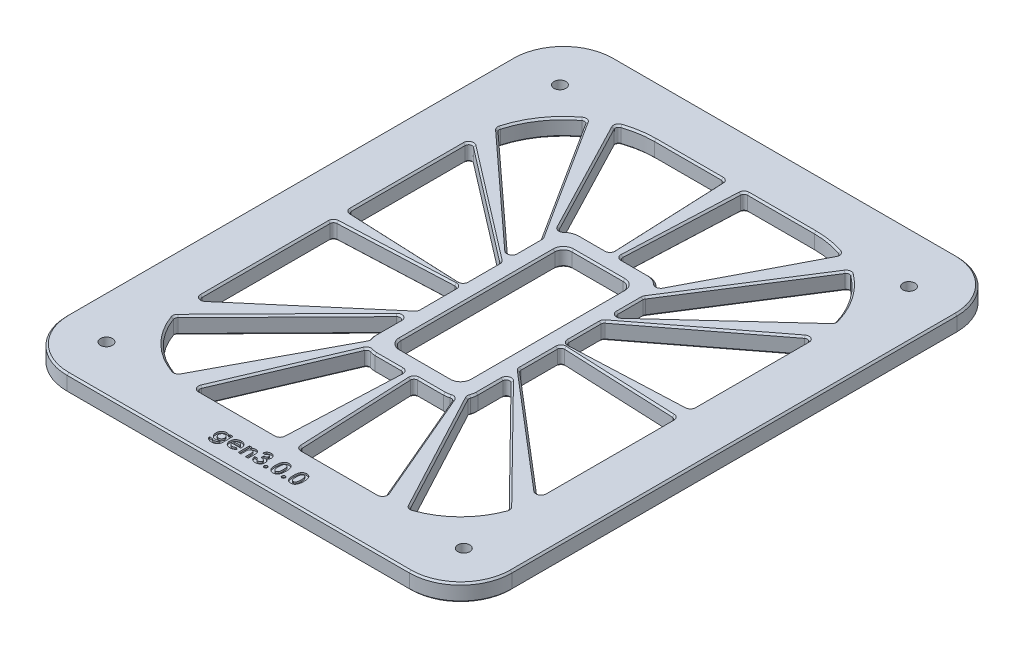
SolidWorks part; units mm, degrees
ref_plane "Front Plane" through (0, 0, 0) normal (0, 0, 1) x (1, 0, 0)
ref_plane "Top Plane" through (0, 0, 0) normal (0, 1, 0) x (1, 0, 0)
ref_plane "Right Plane" through (0, 0, 0) normal (1, 0, 0) x (0, 0, -1)
sketch "Sketch1" plane through (0, 0, 0) normal (0, 1, 0) x (1, 0, 0)
  line L0 (0, 0) -> (0, 160) construction
  line L12 (65, 15) -> (65, 145)
  line L13 (-50, 0) -> (50, 0)
  line L14 (-65, 145) -> (-65, 15)
  line L15 (50, 160) -> (-50, 160)
  circle A3 centre (51, 145) radius 1.75
  arc A8 (50, 0) -> (65, 15) centre (50, 15) ccw
  arc A9 (-65, 15) -> (-50, 0) centre (-50, 15) ccw
  arc A10 (-50, 160) -> (-65, 145) centre (-50, 145) ccw
  arc A11 (65, 145) -> (50, 160) centre (50, 145) ccw
  circle A12 centre (-51, 145) radius 1.75
  circle A13 centre (52.22, 13.7) radius 1.75
  circle A16 centre (-52.22, 13.7) radius 1.75
  dimension "D2" = 3.5
  dimension "D5" = 15
  dimension "D7" = 3.5
  dimension "D9" = 15
  dimension "D10" = 15
  dimension "D11" = 15
  dimension "D12" = 15
  dimension "D3" = 12.78
  dimension "D4" = 13.7
  dimension "D6" = 51
  dimension "D1" = 160
  dimension "D8" = 130
  dimension "D13" = 100
  dimension "D14" = 130
  dimension "D15" = 65
  dimension "D16" = 15
  dimension "D17" = 15
  dimension "D18" = 15
  dimension "D19" = 15
extrude "Boss-Extrude1" add sketch "Sketch1" along normal blind 5
chamfer "Chamfer1" distance 1.55 angle 45 4 edges at (52.22, 0, -11.95) (51, 0, -143.25) (-52.22, 0, -15.45) (-51, 0, -146.75)
sketch "Sketch3" plane through (0, 0, 0) normal (0, -1, 0) x (1, 0, 0)
  line L3 (-50, -80) -> (-50, -145) construction
  line L4 (0, 0) -> (0, -160) construction
  line L5 (-50, 0) -> (50, 0) construction
  line L6 (50, -160) -> (-50, -160) construction
  line L8 (50, -145) -> (50, -15)
  line L9 (50, -15) -> (-50, -15)
  line L10 (-50, -15) -> (-50, -145)
  line L11 (-50, -145) -> (50, -145)
  line L12 (50, -145) -> (50, -80) construction
  line L13 (50, -15) -> (-50, -15) construction
  line L14 (-50, -15) -> (-50, -37.343) construction
  line L15 (-50, -145) -> (0, -145) construction
  line L16 (50, -37.343) -> (50, -80) construction
  line L17 (0, -145) -> (23.3558, -145) construction
  line L18 (-50, -80) -> (-50, -37.343) construction
  line L19 (-65, -80) -> (65, -80) construction
  line L20 (-65, -145) -> (-65, -15) construction
  line L21 (65, -15) -> (65, -145) construction
  line L22 (50, -37.343) -> (50, -15) construction
  line L27 (23.3558, -145) -> (50, -145) construction
  line L28 (50, -118.3558) -> (50, -80) construction
  line L29 (0, -80) -> (2.838, -15) construction
  line L30 (2.838, -15) -> (27.657, -15)
  line L31 (0, -80) -> (27.657, -15) construction
  line L32 (0, -80) -> (34.1235, -15.9562) construction
  line L33 (0, -80) -> (50, -37.343) construction
  line L34 (0, -80) -> (48.8691, -30.3246) construction
  line L35 (0, -80) -> (50, -77.817) construction
  line L36 (0, -80) -> (50, -82.183) construction
  line L37 (0, -80) -> (50, -118.3558) construction
  line L38 (0, -80) -> (49.1513, -125.0269) construction
  line L39 (0, -80) -> (2.838, -145) construction
  line L40 (0, -80) -> (38.4312, -140.325) construction
  line L41 (0, -80) -> (32.9137, -143.2267) construction
  line L42 (27.657, -15) -> (12.4837, -50.6605)
  line L43 (2.838, -15) -> (1.3098, -50)
  line L44 (14.4912, -52.8025) -> (34.1235, -15.9562)
  line L45 (15, -64.7525) -> (48.8691, -30.3246)
  line L46 (15, -67.2029) -> (50, -37.343)
  line L47 (50, -37.343) -> (50, -77.817)
  line L48 (50, -77.817) -> (15, -79.3451)
  line L49 (50, -82.183) -> (15, -80.6549)
  line L50 (50, -82.183) -> (50, -118.3558)
  line L51 (50, -118.3558) -> (15, -91.5067)
  line L52 (49.1513, -125.0269) -> (15, -93.7413)
  line L53 (15, -103.5453) -> (38.4312, -140.325)
  line L54 (32.9137, -143.2267) -> (14.3225, -107.5132)
  line L55 (1.3098, -110) -> (2.838, -145)
  line L56 (2.838, -145) -> (23.3558, -145)
  line L73 (1.3098, -50) -> (10, -50)
  line L74 (15, -55) -> (15, -64.7525)
  line L75 (10, -110) -> (1.3098, -110)
  line L76 (15, -67.2029) -> (15, -79.3451)
  line L77 (15, -80.6549) -> (15, -91.5067)
  line L78 (15, -93.7413) -> (15, -103.5453)
  line L79 (-7.5, -105) -> (7.5, -105)
  line L80 (10, -102.5) -> (10, -57.5)
  line L81 (10, -105) -> (10, -55)
  line L82 (10, -55) -> (-10, -55)
  line L83 (-10, -55) -> (-10, -105)
  line L84 (-10, -105) -> (10, -105)
  line L85 (10, -105) -> (10, -55) construction
  line L86 (10, -55) -> (-10, -55) construction
  line L87 (-10, -55) -> (-10, -105) construction
  line L88 (-10, -105) -> (10, -105) construction
  line L89 (-7.5, -55) -> (7.5, -55)
  line L90 (-10, -102.5) -> (-10, -57.5)
  line L91 (-32.9137, -143.2267) -> (-14.3225, -107.5132)
  line L92 (-2.838, -145) -> (-23.3558, -145)
  line L93 (15, -110) -> (15, -50)
  line L94 (15, -50) -> (-15, -50)
  line L95 (-15, -50) -> (-15, -110)
  line L96 (-15, -110) -> (15, -110)
  line L97 (15, -110) -> (15, -50) construction
  line L98 (15, -50) -> (-15, -50) construction
  line L99 (-15, -50) -> (-15, -110) construction
  line L100 (-15, -110) -> (15, -110) construction
  line L101 (-1.3098, -110) -> (-2.838, -145)
  line L102 (-10, -110) -> (-1.3098, -110)
  line L103 (-15, -103.5453) -> (-38.4312, -140.325)
  line L104 (-15, -93.7413) -> (-15, -103.5453)
  line L105 (-49.1513, -125.0269) -> (-15, -93.7413)
  line L106 (-50, -82.183) -> (-50, -118.3558)
  line L107 (-50, -118.3558) -> (-15, -91.5067)
  line L108 (-15, -80.6549) -> (-15, -91.5067)
  line L109 (-50, -82.183) -> (-15, -80.6549)
  line L110 (-15, -67.2029) -> (-15, -79.3451)
  line L111 (-50, -77.817) -> (-15, -79.3451)
  line L112 (-50, -37.343) -> (-50, -77.817)
  line L113 (-15, -67.2029) -> (-50, -37.343)
  line L114 (-14.4912, -52.8025) -> (-34.1235, -15.9562)
  line L115 (-15, -64.7525) -> (-48.8691, -30.3246)
  line L116 (-15, -55) -> (-15, -64.7525)
  line L117 (-2.838, -15) -> (-1.3098, -50)
  line L118 (-2.838, -15) -> (-27.657, -15)
  line L119 (-27.657, -15) -> (-12.4837, -50.6605)
  line L120 (-1.3098, -50) -> (-10, -50)
  circle A5 centre (51, -145) radius 11.75
  circle A6 centre (51, -145) radius 11.75 construction
  arc A7 (23.3558, -145) -> (32.9137, -143.2267) centre (23.3558, -118.3558) ccw
  circle A8 centre (-52.22, -13.7) radius 11.75
  circle A9 centre (-52.22, -13.7) radius 11.75 construction
  arc A10 (27.657, -15) -> (50, -37.343) centre (27.657, -37.343) cw construction
  circle A11 centre (52.22, -13.7) radius 11.75
  circle A12 centre (52.22, -13.7) radius 11.75 construction
  arc A13 (50, -118.3558) -> (23.3558, -145) centre (23.3558, -118.3558) cw construction
  arc A20 (38.4312, -140.325) -> (49.1513, -125.0269) centre (23.3558, -118.3558) ccw
  arc A25 (34.1235, -15.9562) -> (48.8691, -30.3246) centre (27.657, -37.343) cw
  circle A36 centre (10, -55) radius 5 construction
  circle A37 centre (10, -105) radius 5 construction
  arc A38 (10, -50) -> (12.4837, -50.6605) centre (10, -55) cw
  arc A39 (10, -110) -> (14.3225, -107.5132) centre (10, -105) ccw
  arc A40 (14.4912, -52.8025) -> (15, -55) centre (10, -55) cw
  circle A41 centre (7.5, -57.5) radius 2.5 construction
  circle A42 centre (7.5, -102.5) radius 2.5 construction
  arc A43 (7.5, -55) -> (10, -57.5) centre (7.5, -57.5) cw
  arc A44 (10, -102.5) -> (7.5, -105) centre (7.5, -102.5) cw
  arc A45 (-7.5, -55) -> (-10, -57.5) centre (-7.5, -57.5) ccw
  arc A46 (-10, -102.5) -> (-7.5, -105) centre (-7.5, -102.5) ccw
  arc A47 (-10, -110) -> (-14.3225, -107.5132) centre (-10, -105) cw
  arc A48 (-23.3558, -145) -> (-32.9137, -143.2267) centre (-23.3558, -118.3558) cw
  arc A49 (-38.4312, -140.325) -> (-49.1513, -125.0269) centre (-23.3558, -118.3558) cw
  arc A50 (-14.4912, -52.8025) -> (-15, -55) centre (-10, -55) ccw
  arc A51 (-34.1235, -15.9562) -> (-48.8691, -30.3246) centre (-27.657, -37.343) ccw
  arc A52 (-10, -50) -> (-12.4837, -50.6605) centre (-10, -55) ccw
  circle A55 centre (-51, -145) radius 11.75
  circle A56 centre (-51, -145) radius 11.75 construction
  point P85 (0, -55)
  point P90 (0, -105)
  dimension "D6" = 10
  dimension "D7" = 10
  dimension "D19" = 5
  dimension "D20" = 5
  dimension "D21" = 10
  dimension "D8" = 2.5
  dimension "D9" = 5
  dimension "D10" = 5
  dimension "D11" = 2.5
  dimension "D12" = 2.5
  dimension "D13" = 5
  dimension "D14" = 5
  dimension "D15" = 2.5
  dimension "D16" = 25
  dimension "D2" = 10
  dimension "D3" = 10
  dimension "D4" = 10
  dimension "D5" = 15
  dimension "D17" = 55
  dimension "D18" = 50
extrude "Cut-Extrude1" cut sketch "Sketch3" against normal up to next
sketch "Sketch4" plane through (0, 5, 0) normal (0, 1, 0) x (1, 0, 0)
  line L0 (-50, 0) -> (50, 0) construction
  line L1 (-65, 145) -> (-65, 15) construction
  text T0 "<b>gen3.0.0</b>" font "Century Gothic" height 4.5
  dimension "D1" = 5
  dimension "D2" = 51.5
extrude "Cut-Extrude2" cut sketch "Sketch4" against normal blind 0.5
fillet "Fillet1" radius 1 48 edges at (-15, 2.5, -93.7413) (-14.4912, 2.5, -52.8025) (-15, 2.5, -64.7525) (-48.8691, 2.5, -30.3246) (-34.1235, 2.5, -15.9562) (-27.657, 2.5, -15) (-12.4837, 2.5, -50.6605) (-1.3098, 2.5, -50) (-2.838, 2.5, -15) (27.657, 2.5, -15) (12.4837, 2.5, -50.6605) (1.3098, 2.5, -50) (2.838, 2.5, -15) (34.1235, 2.5, -15.9562) (48.8691, 2.5, -30.3246) (14.4912, 2.5, -52.8025) (15, 2.5, -64.7525) (15, 2.5, -79.3451) (50, 2.5, -77.817) (50, 2.5, -37.343) (50, 2.5, -82.183) (15, 2.5, -91.5067) (-14.3225, 2.5, -107.5132) (-1.3098, 2.5, -110) (-15, 2.5, -79.3451) (-50, 2.5, -77.817) (-15, 2.5, -67.2029) (-15, 2.5, -80.6549) (-50, 2.5, -118.3558) (-50, 2.5, -82.183) (-50, 2.5, -37.343) (15, 2.5, -67.2029) (15, 2.5, -80.6549) (15, 2.5, -93.7413) (15, 2.5, -103.5453) (49.1513, 2.5, -125.0269) (32.9137, 2.5, -143.2267) (14.3225, 2.5, -107.5132) (1.3098, 2.5, -110) (2.838, 2.5, -145) (-49.1513, 2.5, -125.0269) (-32.9137, 2.5, -143.2267) (38.4312, 2.5, -140.325) (50, 2.5, -118.3558) (-15, 2.5, -91.5067) (-15, 2.5, -103.5453) (-38.4312, 2.5, -140.325) (-2.838, 2.5, -145)
chamfer "Chamfer2" distance 0.5 angle 45 240 edges at (60.6066, 0, -155.6066) (65, 0, -80) (60.6066, 0, -4.3934) (0, 0, -160) (-60.6066, 0, -155.6066) (0, 0, 0) (-65, 0, -80) (-60.6066, 0, -4.3934) (60.6066, 5, -155.6066) (0, 5, -160) (65, 5, -80) (60.6066, 5, -4.3934) (0, 5, 0) (-60.6066, 5, -155.6066) (-60.6066, 5, -4.3934) (-65, 5, -80) (10, 0, -80) (9.2678, 0, -55.7322) (9.2678, 0, -104.2678) (0, 0, -55) (0, 0, -105) (-9.2678, 0, -55.7322) (-9.2678, 0, -104.2678) (-10, 0, -80) (-31.851, 0, -52.8267) (-49.4189, 0, -38.6026) (-15.092, 0, -67.2453) (-50, 0, -58.1851) (-15, 0, -72.9824) (-49.7224, 0, -77.5512) (-15.3085, 0, -79.0228) (-32.5436, 0, -78.5791) (-24.2239, 0, -34.536) (-14.6024, 0, -52.786) (-34.2465, 0, -16.2345) (-14.9161, 0, -54.0877) (-43.329, 0, -21.4183) (-15, 0, -58.655) (-48.6981, 0, -30.2787) (-15.6211, 0, -63.2355) (-32.5734, 0, -46.8892) (-2.0758, 0, -32.4564) (-1.6321, 0, -49.6915) (-3.1037, 0, -15.2776) (-6.1772, 0, -50) (-14.97, 0, -15) (-10.8294, 0, -50.0693) (-26.9789, 0, -15.4484) (-12.3686, 0, -50.2443) (-19.974, 0, -33.0566) (19.974, 0, -33.0566) (12.3686, 0, -50.2443) (26.9789, 0, -15.4484) (10.8294, 0, -50.0693) (14.97, 0, -15) (6.1772, 0, -50) (3.1037, 0, -15.2776) (1.6321, 0, -49.6915) (2.0758, 0, -32.4564) (32.5734, 0, -46.8892) (15.6211, 0, -63.2355) (48.6981, 0, -30.2787) (15, 0, -58.655) (43.329, 0, -21.4183) (14.9161, 0, -54.0877) (34.2465, 0, -16.2345) (14.6024, 0, -52.786) (24.2239, 0, -34.536) (32.5436, 0, -78.5791) (49.7224, 0, -77.5512) (15.3085, 0, -79.0228) (50, 0, -58.1851) (15, 0, -72.9824) (49.4189, 0, -38.6026) (15.092, 0, -67.2453) (31.851, 0, -52.8267) (31.8913, 0, -104.4644) (49.4423, 0, -117.2252) (15.1032, 0, -91.4559) (50, 0, -99.7343) (15, 0, -86.3565) (49.7224, 0, -82.4488) (15.3085, 0, -80.9772) (32.5436, 0, -81.4209) (26.5103, 0, -121.6129) (38.5275, 0, -139.881) (15.04, 0, -103.5336) (45.3058, 0, -133.4591) (15, 0, -99.6337) (48.989, 0, -125.0801) (15.5972, 0, -95.0983) (32.689, 0, -109.9459) (2.0758, 0, -127.5436) (3.1037, 0, -144.7224) (1.6321, 0, -110.3085) (13.5755, 0, -145) (6.1772, 0, -110) (27.6415, 0, -144.6531) (11.8608, 0, -109.6409) (32.4254, 0, -143.0475) (14.3084, 0, -108.3515) (23.7086, 0, -125.5438) (-23.7086, 0, -125.5438) (-32.4254, 0, -143.0475) (-14.3084, 0, -108.3515) (-27.6415, 0, -144.6531) (-11.8608, 0, -109.6409) (-13.5755, 0, -145) (-6.1772, 0, -110) (-3.1037, 0, -144.7224) (-1.6321, 0, -110.3085) (-2.0758, 0, -127.5436) (-32.689, 0, -109.9459) (-48.989, 0, -125.0801) (-15.5972, 0, -95.0983) (-45.3058, 0, -133.4591) (-15, 0, -99.6337) (-38.5275, 0, -139.881) (-15.04, 0, -103.5336) (-26.5103, 0, -121.6129) (-32.5436, 0, -81.4209) (-49.7224, 0, -82.4488) (-15.3085, 0, -80.9772) (-50, 0, -99.7343) (-15, 0, -86.3565) (-49.4423, 0, -117.2252) (-15.1032, 0, -91.4559) (-31.8913, 0, -104.4644) (10, 5, -80) (9.2678, 5, -55.7322) (9.2678, 5, -104.2678) (0, 5, -55) (0, 5, -105) (-9.2678, 5, -55.7322) (-9.2678, 5, -104.2678) (-10, 5, -80) (-31.8913, 5, -104.4644) (-15.1032, 5, -91.4559) (-49.4423, 5, -117.2252) (-15, 5, -86.3565) (-50, 5, -99.7343) (-15.3085, 5, -80.9772) (-49.7224, 5, -82.4488) (-32.5436, 5, -81.4209) (-26.5103, 5, -121.6129) (-15.04, 5, -103.5336) (-38.5275, 5, -139.881) (-15, 5, -99.6337) (-45.3058, 5, -133.4591) (-15.5972, 5, -95.0983) (-48.989, 5, -125.0801) (-32.689, 5, -109.9459) (-2.0758, 5, -127.5436) (-1.6321, 5, -110.3085) (-3.1037, 5, -144.7224) (-6.1772, 5, -110) (-13.5755, 5, -145) (-11.8608, 5, -109.6409) (-27.6415, 5, -144.6531) (-14.3084, 5, -108.3515) (-32.4254, 5, -143.0475) (-23.7086, 5, -125.5438) (23.7086, 5, -125.5438) (14.3084, 5, -108.3515) (32.4254, 5, -143.0475) (11.8608, 5, -109.6409) (27.6415, 5, -144.6531) (6.1772, 5, -110) (13.5755, 5, -145) (1.6321, 5, -110.3085) (3.1037, 5, -144.7224) (2.0758, 5, -127.5436) (32.689, 5, -109.9459) (15.5972, 5, -95.0983) (48.989, 5, -125.0801) (15, 5, -99.6337) (45.3058, 5, -133.4591) (15.04, 5, -103.5336) (38.5275, 5, -139.881) (26.5103, 5, -121.6129) (32.5436, 5, -81.4209) (15.3085, 5, -80.9772) (49.7224, 5, -82.4488) (15, 5, -86.3565) (50, 5, -99.7343) (15.1032, 5, -91.4559) (49.4423, 5, -117.2252) (31.8913, 5, -104.4644) (31.851, 5, -52.8267) (15.092, 5, -67.2453) (49.4189, 5, -38.6026) (15, 5, -72.9824) (50, 5, -58.1851) (15.3085, 5, -79.0228) (49.7224, 5, -77.5512) (32.5436, 5, -78.5791) (14.6024, 5, -52.786) (24.2239, 5, -34.536) (14.9161, 5, -54.0877) (34.2465, 5, -16.2345) (15, 5, -58.655) (43.329, 5, -21.4183) (15.6211, 5, -63.2355) (48.6981, 5, -30.2787) (32.5734, 5, -46.8892) (1.6321, 5, -49.6915) (2.0758, 5, -32.4564) (6.1772, 5, -50) (3.1037, 5, -15.2776) (10.8294, 5, -50.0693) (14.97, 5, -15) (12.3686, 5, -50.2443) (26.9789, 5, -15.4484) (19.974, 5, -33.0566) (-12.3686, 5, -50.2443) (-19.974, 5, -33.0566) (-10.8294, 5, -50.0693) (-26.9789, 5, -15.4484) (-6.1772, 5, -50) (-14.97, 5, -15) (-1.6321, 5, -49.6915) (-3.1037, 5, -15.2776) (-2.0758, 5, -32.4564) (-15.6211, 5, -63.2355) (-32.5734, 5, -46.8892) (-15, 5, -58.655) (-48.6981, 5, -30.2787) (-14.9161, 5, -54.0877) (-43.329, 5, -21.4183) (-14.6024, 5, -52.786) (-34.2465, 5, -16.2345) (-24.2239, 5, -34.536) (-32.5436, 5, -78.5791) (-15.3085, 5, -79.0228) (-49.7224, 5, -77.5512) (-15, 5, -72.9824) (-50, 5, -58.1851) (-15.092, 5, -67.2453) (-49.4189, 5, -38.6026) (-31.851, 5, -52.8267)
